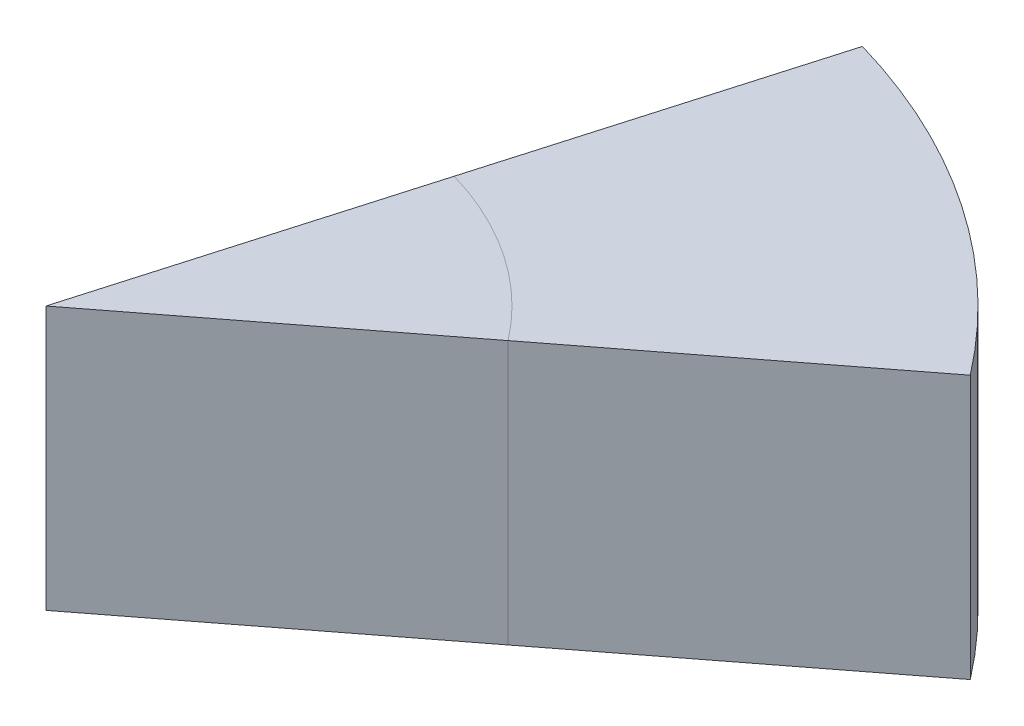
SolidWorks part; units mm, degrees
ref_plane "Front Plane" through (0, 0, 0) normal (0, 0, 1) x (1, 0, 0)
ref_plane "Top Plane" through (0, 0, 0) normal (0, 1, 0) x (1, 0, 0)
ref_plane "Right Plane" through (0, 0, 0) normal (1, 0, 0) x (0, 0, -1)
other "Configuration Table"
sketch "Sketch2" plane through (0, 0, 0) normal (0, 1, 0) x (1, 0, 0)
  line L0 (0, 0) -> (6.9575, 24.0123)
  line L1 (0, 0) -> (19.8041, 15.2577)
  arc A0 (6.9575, 24.0123) -> (19.8041, 15.2577) centre (0, 0) cw
sheet metal parameters "Sheet-Metal1" thickness 10 parameters "D1"=0.7366
base flange "Base-Flange1" sketch "Sketch2" thickness 10 reverse thickness direction yes parameters "D1"=0.7366
sketch "Sketch4" plane through (0, 10, 0) normal (0, 1, 0) x (1, 0, 0)
  line L0 (6.9575, 24.0123) -> (0, 0) construction
  line L1 (0, 0) -> (19.8041, 15.2577) construction
  arc A0 (3.4788, 12.0062) -> (9.902, 7.6289) centre (0, 0) cw
sketch "Sketch5" plane through (0, 0, 0) normal (0.6103, 0, 0.7922) x (0.7922, 0, -0.6103)
  line L0 (12.5, 10) -> (12.5, 0)
  line L1 (0, 0) -> (25, 0) construction
sketch "Sketch6" plane through (0, 0, 0) normal (0, -1, 0) x (1, 0, 0)
  line L0 (6.9575, -24.0123) -> (0, 0) construction
  arc A0 (9.902, -7.6289) -> (3.4788, -12.0062) centre (0, 0) cw
sketch "Sketch7" plane through (0, 0, 0) normal (-0.9605, 0, -0.2783) x (-0.2783, 0, 0.9605)
  line L0 (-12.5, 0) -> (-12.5, 10)
split line "Split Line1"
split line "Split Line2"
split line "Split Line3"
split line "Split Line4"
flat pattern "Flat-Pattern1" [suppressed]
sketch "Bend-Lines1" plane through (0, 0, 0) normal (0, 1, 0) x (-1, 0, 0)
